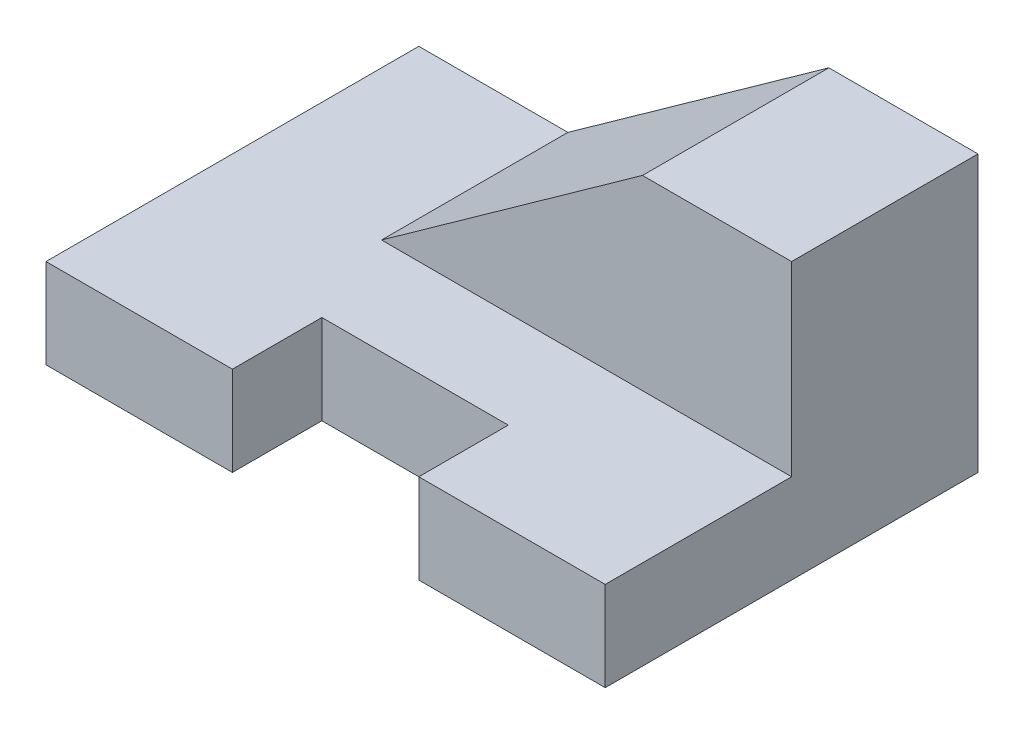
SolidWorks part; units mm, degrees
ref_plane "Front Plane" through (0, 0, 0) normal (0, 0, 1) x (1, 0, 0)
ref_plane "Top Plane" through (0, 0, 0) normal (0, 1, 0) x (1, 0, 0)
ref_plane "Right Plane" through (0, 0, 0) normal (1, 0, 0) x (0, 0, -1)
sketch "Sketch1" plane through (0, 0, 0) normal (0, 0, 1) x (1, 0, 0)
  line L0 (-25, 12) -> (-25, 0)
  line L1 (-75, 12) -> (0, 12)
  line L2 (-75, 12) -> (-75, 0)
  line L3 (-75, 0) -> (0, 0)
  line L4 (0, 12) -> (0, 0)
  line L5 (-75, 12) -> (0, 0) construction
  line L6 (-75, 0) -> (0, 12) construction
  line L7 (-50, 12) -> (-50, 0)
  line L8 (0, 12) -> (0, 37)
  line L9 (0, 37) -> (-20, 37)
  line L10 (-20, 37) -> (-55, 12)
  point P0 (-37.5, 6)
  point P15 (-30.2117, -1.2927)
  point P16 (-27.2694, 3.8677)
  dimension "D1" = 12
  dimension "D2" = 25
  dimension "D3" = 75
  dimension "D4" = 25
  dimension "D5" = 25
  dimension "D6" = 20
  dimension "D7" = 20
extrude "Boss-Extrude1" add sketch "Sketch1" along normal blind 50 contours L4 L1 L0 L3 | L7 L1 L2 L3 region at (-12.5, 6, 0) region at (-62.5, 6, 0)
extrude "Boss-Extrude2" add sketch "Sketch1<3>" along normal blind 38 contours L1 L7 L3 L0 region at (-37.5, 6, 0)
sketch "Sketch1<3>" plane through (0, 0, 0) normal (0, 0, 1) x (1, 0, 0) same geometry as "Sketch1"
extrude "Boss-Extrude3" add sketch "Sketch1<4>" along normal blind 25 contours L9 L10 L1 L8 region at (-20.1111, 22.5556, 0)
sketch "Sketch1<4>" plane through (0, 0, 0) normal (0, 0, 1) x (1, 0, 0) same geometry as "Sketch1"
